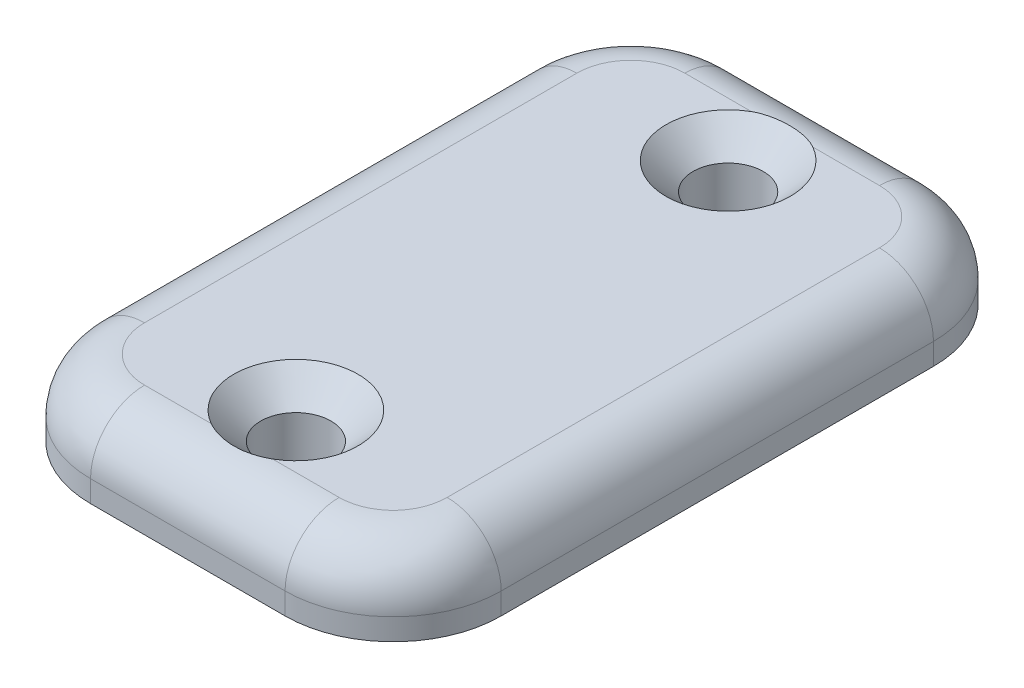
SolidWorks part; units mm, degrees
ref_plane "Front Plane" through (0, 0, 0) normal (0, 0, 1) x (1, 0, 0)
ref_plane "Top Plane" through (0, 0, 0) normal (0, 1, 0) x (1, 0, 0)
ref_plane "Right Plane" through (0, 0, 0) normal (1, 0, 0) x (0, 0, -1)
sketch "Sketch1" plane through (0, 0, 0) normal (0, 0, 1) x (1, 0, 0)
  line L1 (-19, -19) -> (24, -19)
  line L2 (-19, -19) -> (-19, 24)
  line L3 (-19, 24) -> (24, 24)
  line L4 (24, -19) -> (24, 24)
  line L7 (24, -19) -> (29, -19)
  line L8 (24, -19) -> (24, 32.2)
  line L9 (24, 32.2) -> (29, 32.2)
  line L10 (29, -19) -> (29, 32.2)
  line L11 (24, 32.2) -> (-19, 32.2)
  line L12 (24, 32.2) -> (24, 25.2)
  line L13 (24, 25.2) -> (-19, 25.2)
  line L14 (-19, 32.2) -> (-19, 25.2)
  circle A0 centre (0, 0) radius 13.75
  dimension "D1" = 27.5
  dimension "D7" = 19
  dimension "D3" = 19
  dimension "D8" = 24
  dimension "D2" = 1.2
  dimension "D4" = 24
  dimension "D5" = 5
  dimension "D6" = 7
extrude "Boss-Extrude1" add sketch "Sketch1" along normal blind 60 contours L1 L4 L3 L2 A0 | L11 L14 L13 L8 | L7 L10 L9 L8 L4 region at (-18.3919, 2.5, 0) region at (26.5, 6.6, 0) region at (2.5, 28.7, 0)
sketch "Sketch2" plane through (0, 0, 60) normal (0, 0, 1) x (1, 0, 0)
  line L0 (0, 0) -> (0, 32.2) construction
  line L1 (-19, 32.2) -> (29, 32.2) construction
sketch "Sketch3" plane through (0, 32.2, 0) normal (0, 1, 0) x (1, 0, 0)
  line L2 (-19, -30) -> (29, -30) construction
  line L3 (-19, -60) -> (-19, 0) construction
  line L4 (29, -60) -> (29, 0) construction
  circle A0 centre (0, -50) radius 3.25
  circle A1 centre (0, -10) radius 3.25
  dimension "D1" = 6.5
  dimension "D2" = 40
extrude "Cut-Extrude5" cut sketch "Sketch3" against normal through all
chamfer "Chamfer2" distance 2.5 angle 45 2 edges at (0, 32.2, 53.25) (0, 32.2, 6.75)
sketch "Sketch7" plane through (0, -19, 0) normal (0, -1, 0) x (1, 0, 0)
  line L0 (-19, 30) -> (29, 30) construction
  line L1 (0, 43.5337) -> (5.6, 46.7668)
  line L2 (5.6, 46.7668) -> (5.6, 53.2332)
  line L3 (5.6, 53.2332) -> (0, 56.4663)
  line L4 (0, 56.4663) -> (-5.6, 53.2332)
  line L5 (-5.6, 53.2332) -> (-5.6, 46.7668)
  line L6 (-5.6, 46.7668) -> (0, 43.5337)
  line L7 (-19, 60) -> (-19, 0) construction
  line L8 (29, 60) -> (29, 0) construction
  line L9 (-5.6, 13.2332) -> (0, 16.4663)
  line L10 (-5.6, 6.7668) -> (-5.6, 13.2332)
  line L11 (0, 3.5337) -> (-5.6, 6.7668)
  line L12 (5.6, 6.7668) -> (0, 3.5337)
  line L13 (5.6, 13.2332) -> (5.6, 6.7668)
  line L14 (0, 16.4663) -> (5.6, 13.2332)
  circle A0 centre (0, 50) radius 5.6 construction
  dimension "D1" = 11.2
extrude "Cut-Extrude6" cut sketch "Sketch7" along normal blind 15 from offset 38 offset against normal yes
sketch "Sketch9" plane through (0, 0, 0) normal (0, 0, -1) x (-1, 0, 0)
  line L0 (-13.75, 0) -> (-19, 0) construction
  line L1 (19, -19) -> (-29, -19) construction
  line L2 (-19, -19) -> (-29, -19)
  line L3 (-19, -19) -> (-19, 32.2)
  line L4 (-19, 32.2) -> (-29, 32.2)
  line L5 (-29, -19) -> (-29, 32.2)
  circle A0 centre (0, 0) radius 13.75 construction
  dimension "D1" = 5.25
extrude "Cut-Extrude7" cut sketch "Sketch9" against normal through all
fillet "Fillet1" radius 5 4 edges at (0, 32.2, 60) (19, 32.2, 30) (0, 32.2, 0) (-19, 32.2, 30)
fillet "Fillet2" radius 10 8 edges at (-17.5355, 30.7355, 58.5355) (-17.5355, 30.7355, 1.4645) (17.5355, 30.7355, 1.4645) (17.5355, 30.7355, 58.5355) (19, 26.2, 60) (19, 26.2, 0) (-19, 26.2, 0) (-19, 26.2, 60)
